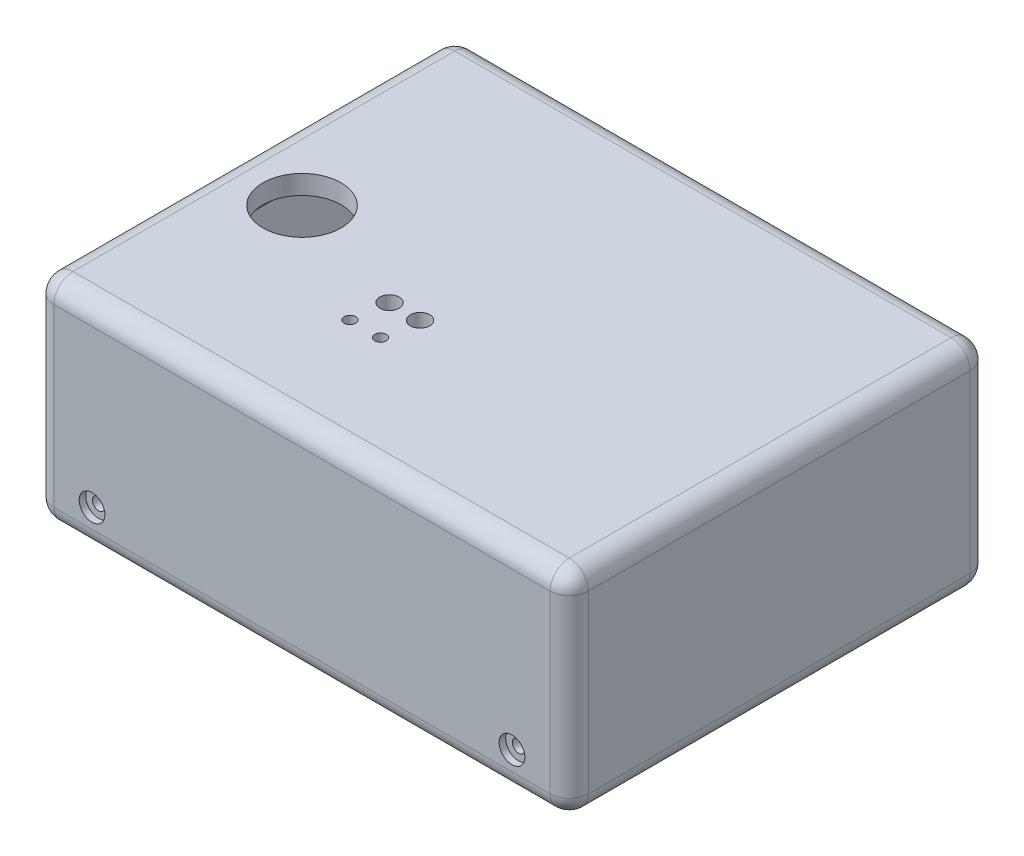
SolidWorks part; units mm, degrees
ref_plane "Front Plane" through (0, 0, 0) normal (0, 0, 1) x (1, 0, 0)
ref_plane "Top Plane" through (0, 0, 0) normal (0, 1, 0) x (1, 0, 0)
ref_plane "Right Plane" through (0, 0, 0) normal (1, 0, 0) x (0, 0, -1)
sketch "Sketch1" plane through (0, 0, 0) normal (0, 1, 0) x (1, 0, 0)
  line L1 (-70, -55) -> (70, -55)
  line L2 (-70, -55) -> (-70, 55)
  line L3 (-70, 55) -> (70, 55)
  line L4 (70, -55) -> (70, 55)
  line L5 (-70, -55) -> (70, 55) construction
  line L6 (-70, 55) -> (70, -55) construction
  point P0 (0, 0)
  dimension "D1" = 140
  dimension "D2" = 110
extrude "Boss-Extrude1" add sketch "Sketch1" along normal blind 56
sketch "Sketch2" plane through (0, 0, 0) normal (0, -1, 0) x (1, 0, 0)
  line L0 (-70, -55) -> (-70, 55) construction
  line L1 (-65, -50) -> (65, -50)
  line L2 (-65, -50) -> (-65, 50)
  line L3 (-65, 50) -> (65, 50)
  line L4 (65, -50) -> (65, 50)
  line L5 (-65, -50) -> (65, 50) construction
  line L6 (-65, 50) -> (65, -50) construction
  line L7 (-70, 55) -> (70, 55) construction
  point P0 (0, 0)
  dimension "D1" = 5
  dimension "D2" = 5
extrude "Cut-Extrude1" cut sketch "Sketch2" against normal blind 51
fillet "Fillet1" radius 5 4 edges at (0, 56, -55) (70, 56, 0) (0, 56, 55) (-70, 56, 0)
fillet "Fillet2" radius 5 8 edges at (-70, 25.5, -55) (70, 25.5, -55) (70, 25.5, 55) (-70, 25.5, 55) (-68.5355, 54.5355, -53.5355) (68.5355, 54.5355, -53.5355) (68.5355, 54.5355, 53.5355) (-68.5355, 54.5355, 53.5355)
fillet "Fillet3" radius 5 4 edges at (65, 51, 0) (0, 51, -50) (-65, 51, 0) (0, 51, 50)
fillet "Fillet4" radius 5 8 edges at (65, 23, 50) (65, 23, -50) (-65, 23, -50) (-65, 23, 50) (63.5355, 49.5355, 48.5355) (63.5355, 49.5355, -48.5355) (-63.5355, 49.5355, -48.5355) (-63.5355, 49.5355, 48.5355)
fillet "Fillet6" radius 5 8 edges at (-68.5355, 0, 53.5355) (-70, 0, 0) (-68.5355, 0, -53.5355) (0, 0, -55) (68.5355, 0, -53.5355) (70, 0, 0) (68.5355, 0, 53.5355) (0, 0, 55)
sketch "Sketch3" plane through (0, 56, 0) normal (0, 1, 0) x (1, 0, 0)
  line L0 (-70, -50) -> (-70, 50) construction
  line L1 (65, -55) -> (-65, -55) construction
  circle A0 centre (-16.48, -15.61) radius 2.54
  circle A1 centre (-8.48, -15.61) radius 2.54
  dimension "D1" = 8
  dimension "D2" = 53.52
  dimension "D3" = 39.39
extrude "Cut-Extrude2" cut sketch "Sketch3" against normal blind 5
sketch "Sketch4" plane through (0, 56, 0) normal (0, 1, 0) x (1, 0, 0)
  line L0 (-65, 50) -> (-65, -50) construction
  line L2 (65, -55) -> (-65, -55) construction
  circle A0 centre (-50, -5) radius 10.25
  dimension "D1" = 20.5
  dimension "D2" = 15
  dimension "D3" = 50
extrude "Cut-Extrude3" cut sketch "Sketch4" against normal blind 5
sketch "Sketch5" plane through (0, 56, 0) normal (0, 1, 0) x (1, 0, 0)
  line L0 (-70, -50) -> (-70, 50) construction
  line L1 (65, -55) -> (-65, -55) construction
  circle A0 centre (-17.725, -24.71) radius 1.5
  circle A1 centre (-9.725, -24.71) radius 1.5
  dimension "D1" = 52.275
  dimension "D2" = 8
  dimension "D3" = 30.29
  dimension "D4" = 30.29
extrude "Cut-Extrude4" cut sketch "Sketch5" against normal blind 5
hole_wizard "CBORE for #4 Binding Head Machine Screw1" positions "Sketch6" profile "Sketch7" counterbore size "#4" standard "ANSI Inch" end condition through all
sketch "Sketch6" plane through (58.9654, 7.3812, 55) normal (0, 0, 1) x (1, 0, 0)
  point P0 (-3.9654, 2.6188)
  point P1 (-113.9654, 2.6188)
sketch "Sketch7" plane through (55, 10, 55) normal (1, 0, 0) x (0, -1, 0)
  line L0 (0, 0) -> (0, 110)
  line L1 (0, 110) -> (1.6319, 110)
  line L2 (1.6319, 110) -> (1.632, 1.7272)
  line L3 (1.632, 1.7272) -> (3.3731, 1.7272)
  line L4 (3.3731, 1.7272) -> (3.3731, 0)
  line L5 (3.3731, 0) -> (0, 0)
  line L6 (0, -6.35) -> (0, 107.95) construction
  dimension "Thru Hole Dia." = 3.2639
  dimension "Thru Hole Depth" = 110
  dimension "C'Bore Dia." = 6.7462
  dimension "C'Bore Depth" = 1.7272
